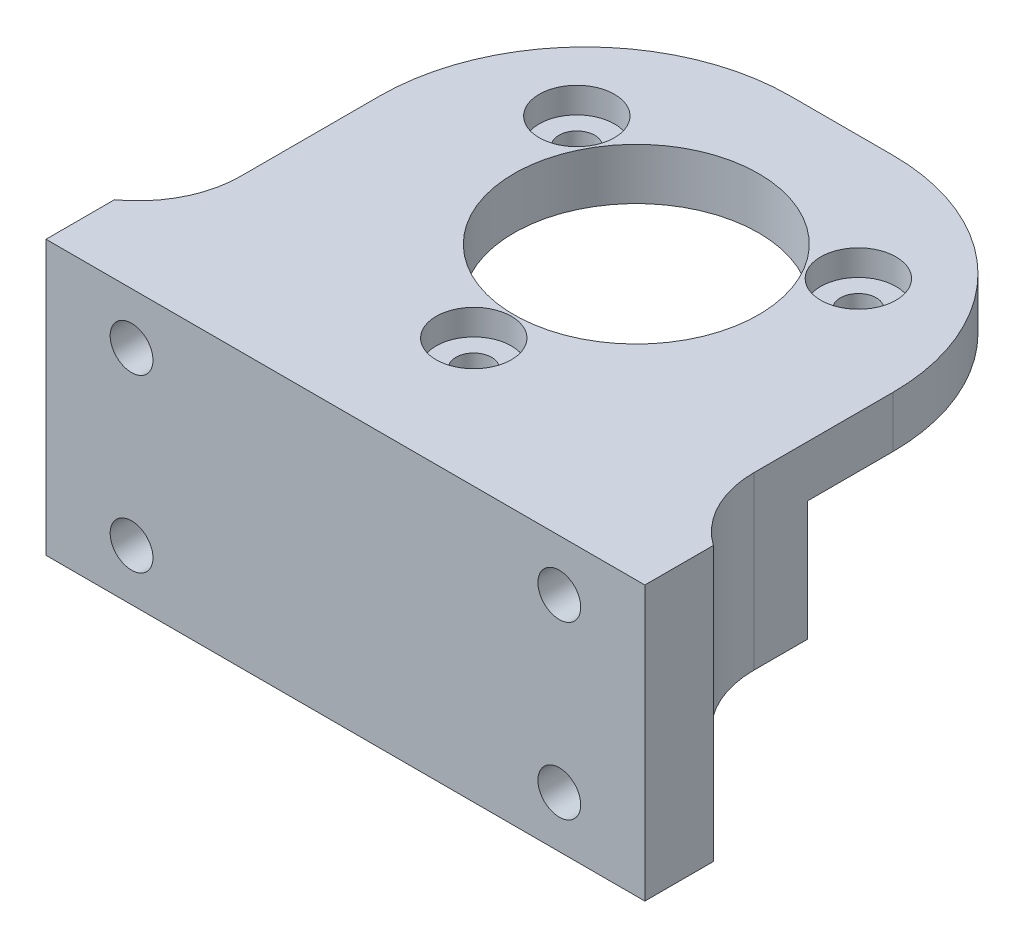
SolidWorks part; units mm, degrees
ref_plane "Front Plane" through (0, 0, 0) normal (0, 0, 1) x (1, 0, 0)
ref_plane "Top Plane" through (0, 0, 0) normal (0, 1, 0) x (1, 0, 0)
ref_plane "Right Plane" through (0, 0, 0) normal (1, 0, 0) x (0, 0, -1)
sketch "Sketch1" plane through (0, 0, 0) normal (0, 0, 1) x (1, 0, 0)
  line L1 (-15, -5) -> (15, -5)
  line L2 (-15, -5) -> (-15, 5)
  line L3 (-15, 5) -> (15, 5)
  line L4 (15, -5) -> (15, 5)
  line L5 (-15, -5) -> (15, 5) construction
  line L6 (-15, 5) -> (15, -5) construction
  point P0 (0, 0)
  point P11 (0, 0)
  point P13 (0, 0.5)
  dimension "D1" = 30
  dimension "D2" = 10
extrude "Main" add sketch "Sketch1" along normal blind 25
sketch "Sketch5" plane through (0, -5, 0) normal (0, -1, 0) x (-1, 0, 0)
  line L0 (0, -21.5) -> (-8.2272, -7.25) construction
  line L1 (-8.2272, -7.25) -> (8.2272, -7.25) construction
  line L2 (8.2272, -7.25) -> (0, -21.5) construction
  line L4 (15, 0) -> (-15, 0) construction
  circle A0 centre (0, -12) radius 9.5 construction
  circle A1 centre (0, -21.5) radius 1.05
  circle A2 centre (-8.2272, -7.25) radius 1.05
  circle A3 centre (8.2272, -7.25) radius 1.05
  circle A4 centre (0, -12) radius 7.15
  point P11 (0, 0)
  point P12 (0, -12.5)
  point P13 (0, 0)
  point P14 (0, -12.5)
  point P16 (-9.4545, -9.7951)
  point P17 (0, 0)
  point P18 (0, 0)
  dimension "D1" = 19
  dimension "D2" = 2.1
  dimension "D4" = 14.3
  dimension "D3" = 12
extrude "MainAndFixHole" cut sketch "Sketch5" against normal through all
sketch "Sketch6" plane through (0, 5, 0) normal (0, -1, 0) x (-1, 0, 0)
  circle A0 centre (0, -21.5) radius 2.2
  circle A1 centre (-8.2272, -7.25) radius 2.2
  circle A2 centre (8.2272, -7.25) radius 2.2
  dimension "D1" = 4.4
extrude "CoderFixHole2" cut sketch "Sketch6" along normal blind 1.5
sketch "Sketch11" plane through (0, -5, 0) normal (0, 1, 0) x (1, 0, 0)
  line L0 (-15, 0) -> (15, 0)
  line L1 (15, 0) -> (15, -17)
  line L2 (15, -17) -> (10.9087, -17)
  line L3 (-15, 0) -> (-15, -17)
  line L4 (-15, -17) -> (-10.9087, -17)
  line L8 (-15, 0) -> (15, 0) construction
  line L9 (15, -25) -> (15, 0) construction
  arc A0 (10.9087, -17) -> (-10.9087, -17) centre (0, -12) cw
  circle A1 centre (0, -12) radius 7.15 construction
  point P3 (-10.7003, -12)
  point P8 (11, -12.6385)
  point P9 (-12, 0)
  point P11 (0, 0)
  point P12 (-11, -7.2042)
  point P14 (10.8949, -17.0301)
  point P15 (-10.4272, -17.8949)
  point P16 (0, 0)
  point P17 (-10.8136, -17.2024)
  point P18 (-12, 0)
  point P19 (12, -16.3703)
  point P22 (12, -16.5463)
  point P23 (-13.0874, 0)
  point P25 (15, -12.1548)
  point P28 (15, 0)
  point P30 (11.2513, -16.1722)
  point P31 (15, 0)
  point P32 (15, 0)
  dimension "D1" = 12
  dimension "D2" = 5
extrude "CoderHole2" cut sketch "Sketch11" along normal blind 7
sketch "Sketch10" plane through (0, 0, 25) normal (0, 0, 1) x (1, 0, 0)
  line L0 (-15, -5) -> (15, -5) construction
  line L1 (-17.5, -11) -> (17.5, -11)
  line L2 (-17.5, -11) -> (-17.5, 5)
  line L3 (-17.5, 5) -> (17.5, 5)
  line L4 (17.5, -11) -> (17.5, 5)
  line L5 (15, 5) -> (-15, 5) construction
  point P4 (0, -5)
  point P5 (0, -5)
  point P11 (0, 5)
  dimension "D1" = 16
  dimension "D2" = 35
extrude "Link" add sketch "Sketch10" along normal blind 4
sketch "Sketch8" plane through (0, 0, 29) normal (0, 0, 1) x (1, 0, 0)
  line L0 (17.5, -11) -> (17.5, 5) construction
  line L2 (15, 5) -> (-15, 5) construction
  line L5 (17.5, 5) -> (-17.5, 5) construction
  circle A0 centre (12.5, 2) radius 1.25
  point P2 (11.9581, 0.8054)
  point P3 (17.5, -3)
  point P11 (0, 5)
  dimension "D3" = 2.5
  dimension "D1" = 3
  dimension "D2" = 12.5
  dimension "D4" = 8
extrude "VerticalHoles" cut sketch "Sketch8" against normal up to surface (12 mm away) up to face at (-12.9544, -1.5, 17)
sketch "Sketch13" plane through (0, 0, 25) normal (0, 0, -1) x (-1, 0, 0)
  line L2 (-17.5, -11) -> (-17.5, 5) construction
  line L3 (-12.5, -8) -> (12.5, -8) construction
  circle A0 centre (-12.5, -8) radius 2.5
  circle A1 centre (12.5, -8) radius 2.5
  arc A2 (-13.75, 2) -> (-11.25, 2) centre (-12.5, 2) ccw construction
  point P2 (0, -8)
  dimension "D3" = 5
  dimension "D1" = 10
  dimension "D2" = 5
extrude "LinkReinforcement" add sketch "Sketch13" along normal blind 2
fillet "Fillet4" radius 6 2 edges at (15, 0, 25) (-15, 0, 25)
fillet "Fillet6" radius 12 2 edges at (15, 3.5, 0) (-15, 3.5, 0)
pattern_linear "HoleLPattern1" count 2 spacing 25 along (-1, 0, 0) count 2 spacing 10 along (0, -1, 0) of "VerticalHoles"
